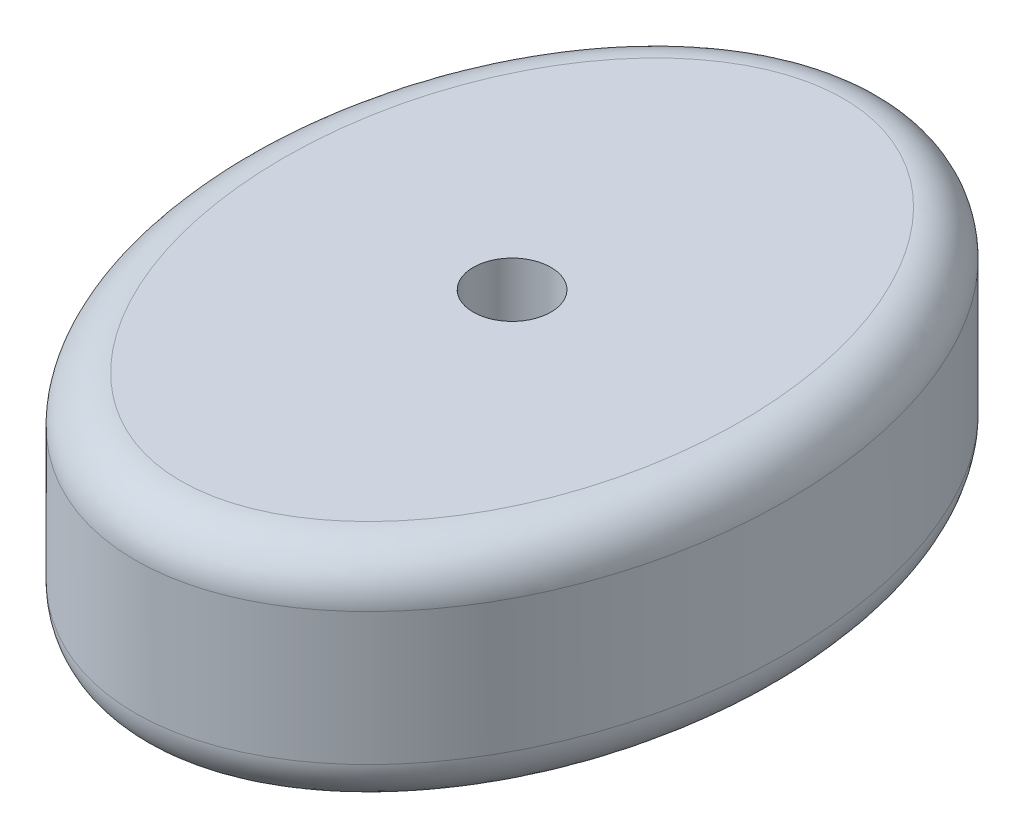
SolidWorks part; units mm, degrees
ref_plane "Front Plane" through (0, 0, 0) normal (0, 0, 1) x (1, 0, 0)
ref_plane "Top Plane" through (0, 0, 0) normal (0, 1, 0) x (1, 0, 0)
ref_plane "Right Plane" through (0, 0, 0) normal (1, 0, 0) x (0, 0, -1)
sketch "Sketch1" plane through (0, 0, 0) normal (0, 1, 0) x (1, 0, 0)
  line L0 (-6, 0) -> (6, 0) construction
  circle A6 centre (0, 0) radius 1.975
  ellipse E0 centre (0, 0) end of major axis (0, 8.25) minor radius 6
  dimension "D1" = 3.95
  dimension "D2" = 12
  dimension "D3" = 16.5
extrude "Boss-Extrude1" add sketch "Sketch1" along normal blind 2.4
sketch "Sketch2" plane through (0, 2.4, 0) normal (0, 1, 0) x (1, 0, 0)
  circle A0 centre (0, 0) radius 0.85
  ellipse E0 centre (0, 0) end of major axis (0, 8.25) minor radius 6
  ellipse E1 centre (0, 0) end of major axis (0, 8.25) minor radius 6 construction
  dimension "D1" = 1.7
extrude "Boss-Extrude2" add sketch "Sketch2" along normal blind 2.5
fillet "Fillet1" radius 1 2 edges at (0, 0, -8.25) (0, 4.9, -8.25)
